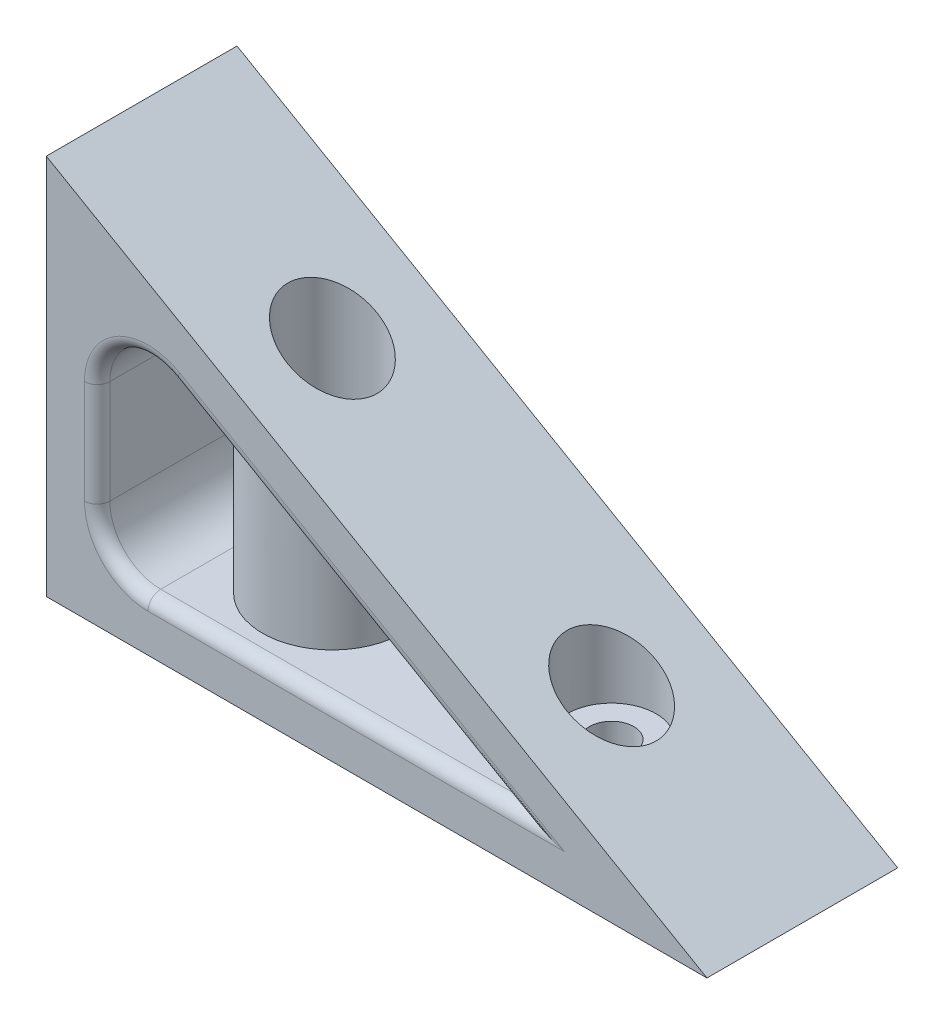
SolidWorks part; units mm, degrees
ref_plane "Front" through (0, 0, 0) normal (0, 0, 1) x (1, 0, 0)
ref_plane "Top" through (0, 0, 0) normal (0, 1, 0) x (1, 0, 0)
ref_plane "Right" through (0, 0, 0) normal (1, 0, 0) x (0, 0, -1)
ref_plane "平面1" through (0, 30, 0) normal (0, 1, 0) x (1, 0, 0)
sketch "ｽｹｯﾁ1" plane through (0, 0, 0) normal (0, 0, 1) x (1, 0, 0)
  line L0 (0, 0) -> (51.9615, 0)
  line L1 (51.9615, 0) -> (0, 30)
  line L2 (0, 30) -> (0, 0)
  dimension "D1" = 60
  dimension "D2" = 30
extrude "ﾎﾞｽ - 押し出し1" add sketch "ｽｹｯﾁ1" along normal blind 15
sketch "ｽｹｯﾁ2" plane through (0, 0, 15) normal (0, 0, 1) x (1, 0, 0)
  line L0 (4, 23.0718) -> (4, 4)
  line L1 (4, 4) -> (37.0333, 4)
  line L2 (37.0333, 4) -> (4, 23.0718)
  line L3 (0, 30) -> (0, 0)
  line L4 (0, 0) -> (51.9615, 0)
  line L5 (51.9615, 0) -> (0, 30)
  line L6 (0, 30) -> (0, 0) construction
  line L7 (0, 0) -> (51.9615, 0) construction
  line L8 (51.9615, 0) -> (0, 30) construction
  dimension "D1" = 0
  dimension "D2" = 4
extrude "ｶｯﾄ - 押し出し2" cut sketch "ｽｹｯﾁ2" against normal through all
sketch "ｽｹｯﾁ4" plane through (0, 0, 0) normal (0, -1, 0) x (-1, 0, 0)
  line L0 (0, 0) -> (-51.9615, 0) construction
  line L1 (0, -15) -> (0, 0) construction
  line L2 (-51.9615, -15) -> (-51.9615, 0) construction
  circle A0 centre (-15, -7.5) radius 1.75
  circle A1 centre (-36.9615, -7.5) radius 1.75
  circle A2 centre (-15, -7.5) radius 5.5
  circle A3 centre (-36.9615, -7.5) radius 5.5
  dimension "D1" = 7.5
  dimension "D2" = 7.5
  dimension "D3" = 15
  dimension "D4" = 15
  dimension "D5" = 3.5
  dimension "D6" = 3.5
  dimension "D7" = 11
  dimension "D8" = 11
extrude "ﾎﾞｽ - 押し出し2" add sketch "ｽｹｯﾁ4" against normal blind 30
sketch "ｽｹｯﾁ5" plane through (0, 30, 0) normal (0, 1, 0) x (1, 0, 0)
  circle A0 centre (36.9615, -7.5) radius 1.75 construction
  circle A1 centre (15, -7.5) radius 1.75 construction
  circle A2 centre (36.9615, -7.5) radius 1.75
  circle A3 centre (15, -7.5) radius 1.75
extrude "ｶｯﾄ - 押し出し3" cut sketch "ｽｹｯﾁ5" against normal through all both and the other way through all
sketch "ｽｹｯﾁ9" plane through (0, 30, 0) normal (0, 1, 0) x (1, 0, 0)
  circle A1 centre (36.9615, -7.5) radius 1.75 construction
  circle A2 centre (15, -7.5) radius 1.75 construction
  circle A3 centre (36.9615, -7.5) radius 1.75 construction
  circle A4 centre (15, -7.5) radius 1.75 construction
  circle A5 centre (15, -7.5) radius 3.5
  circle A6 centre (36.9615, -7.5) radius 3.5
  dimension "D1" = 7
  dimension "D2" = 7
extrude "ｶｯﾄ - 押し出し5" cut sketch "ｽｹｯﾁ9" against normal blind 25 contours A5 | A6
sketch "ｽｹｯﾁ6" plane through (0, 0, 15) normal (0, 0, 1) x (1, 0, 0)
  line L0 (38.7115, 30) -> (35.2115, 30) construction
  line L3 (31.4615, 30) -> (31.4615, 11.8357) construction
  line L4 (9.5, 30) -> (9.5, 24.5152) construction
  line L5 (20.5, 18.1643) -> (20.5, 30) construction
  line L6 (20.5, 30) -> (9.5, 30) construction
  line L7 (42.4615, 30) -> (31.4615, 30)
  line L8 (31.4615, 30) -> (31.4615, 11.8357)
  line L9 (9.5, 30) -> (9.5, 24.5152)
  line L10 (20.5, 18.1643) -> (20.5, 30)
  line L11 (20.5, 30) -> (9.5, 30)
  line L12 (42.4615, 5.4848) -> (42.4615, 30) construction
  line L13 (51.9615, 0) -> (0, 30) construction
  line L14 (42.4615, 5.4848) -> (42.4615, 30)
  line L15 (51.9615, 0) -> (0, 30)
  line M7 (51.9615, 0) -> (0, 30)
extrude "ｶｯﾄ - 押し出し4" cut sketch "ｽｹｯﾁ6" against normal through all contours L14 L8 M7 | L10 L11 L9 M7 region at (37.2343, 19.2514, 15) region at (15.6722, 25.4758, 15)
fillet "ﾌｨﾚｯﾄ1" radius 4 2 edges at (4, 23.0718, 7.5) (4, 4, 7.5)
fillet "ﾌｨﾚｯﾄ2" radius 1 10 edges at (23.5167, 11.8038, 0) (6, 19.6077, 0) (22.5167, 4, 0) (5.1716, 5.1716, 0) (23.5167, 11.8038, 15) (6, 19.6077, 15) (4, 12.0718, 15) (5.1716, 5.1716, 15) (4, 12.0718, 0) (22.5167, 4, 15)
